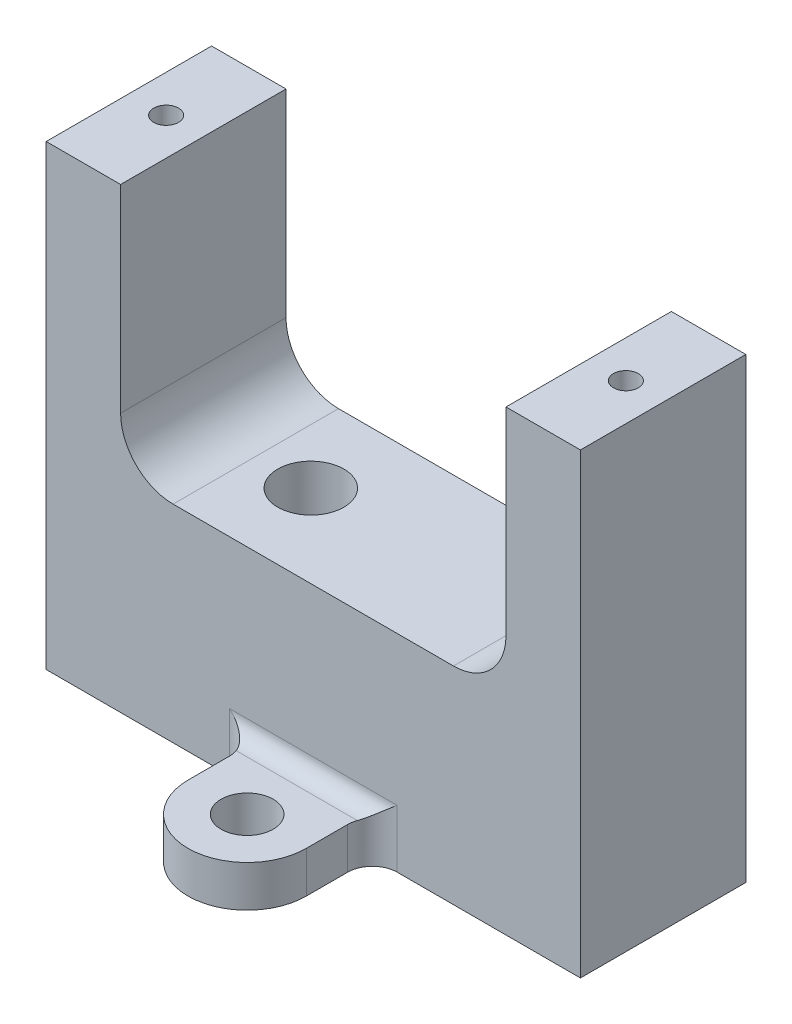
SolidWorks part; units mm, degrees
ref_plane "Front Plane" through (0, 0, 0) normal (0, 0, 1) x (1, 0, 0)
ref_plane "Top Plane" through (0, 0, 0) normal (0, 1, 0) x (1, 0, 0)
ref_plane "Right Plane" through (0, 0, 0) normal (1, 0, 0) x (0, 0, -1)
sketch "Sketch1" plane through (0, 0, 0) normal (0, 1, 0) x (1, 0, 0)
  line L0 (-16.15, 5) -> (-11.65, -5) construction
  line L1 (-16.15, 5) -> (-11.65, 5)
  line L2 (-16.15, 5) -> (-16.15, -5)
  line L3 (-16.15, -5) -> (-11.65, -5)
  line L4 (-11.65, 5) -> (-11.65, -5)
  line L5 (0, 0) -> (0, -5) construction
  line L6 (0, -5) -> (-11.65, -5) construction
  line L7 (16.15, 5) -> (11.65, -5) construction
  line L8 (11.65, 5) -> (11.65, -5)
  line L9 (16.15, -5) -> (11.65, -5)
  line L10 (16.15, 5) -> (16.15, -5)
  line L11 (16.15, 5) -> (11.65, 5)
  circle A0 centre (-13.9, 0) radius 0.75 construction
  circle A2 centre (13.9, 0) radius 0.75 construction
  dimension "D1" = 1.5
  dimension "D2" = 13.9
  dimension "D3" = 10
  dimension "D4" = 4.5
extrude "Boss-Extrude1" add sketch "Sketch1" against normal blind 15.15
hole_wizard "Ø1.5 (1.5) Diameter Hole1" positions "Sketch3" profile "Sketch4" hole size "Ø1.5" standard "ANSI Metric"
sketch "Sketch3" plane through (0, 0, 0) normal (0, 1, 0) x (1, 0, 0)
  line L0 (16.15, 5) -> (11.65, -5) construction
  point P0 (-13.9, 0)
  point P3 (13.9, 0)
sketch "Sketch4" plane through (-13.9, 0, 0) normal (1, 0, 0) x (0, 0, 1)
  line L0 (0, 0) -> (0, 8)
  line L1 (0, 8) -> (0.75, 7.5494)
  line L2 (0.75, 7.5494) -> (0.75, 0)
  line L5 (0.75, 0) -> (0, 0)
  line L10 (0, 8) -> (-0.75, 7.5494) construction
  line L11 (0, -6.35) -> (0, 107.95) construction
  dimension "Hole Dia." = 1.5
  dimension "Hole Depth" = 8
  dimension "Drill Angle" = 118
sketch "Sketch5" plane through (0, -15.15, 0) normal (0, -1, 0) x (1, 0, 0)
  line L4 (-16.15, 5) -> (-16.15, -5)
  line L5 (-16.15, -5) -> (-11.65, -5)
  line L6 (-11.65, -5) -> (-11.65, 5)
  line L7 (-11.65, 5) -> (-16.15, 5)
  line L8 (-16.15, 5) -> (-16.15, -5)
  line L9 (-16.15, -5) -> (16.15, -5)
  line L11 (16.15, 5) -> (-16.15, 5)
  line L12 (11.65, -5) -> (16.15, -5)
  line L13 (16.15, -5) -> (16.15, 5)
  line L14 (16.15, 5) -> (11.65, 5)
  line L15 (11.65, 5) -> (11.65, -5)
  line L17 (16.15, -5) -> (16.15, 5)
  circle A0 centre (-5.15, 0) radius 2
  circle A1 centre (-13.9, 0) radius 0.75 construction
  dimension "D1" = 4
  dimension "D2" = 8.75
  dimension "D3" = 0
  dimension "D4" = 0
extrude "Boss-Extrude2" add sketch "Sketch5" along normal blind 12.5
fillet "Fillet1" radius 3.175 2 edges at (11.65, -15.15, 0) (-11.65, -15.15, 0)
sketch "Sketch6" plane through (-16.15, 0, 0) normal (-1, 0, 0) x (0, 0, 1)
  line L0 (5, -15.15) -> (-5, -15.15) construction
  line L1 (5, -15.15) -> (-5, -15.15) construction
  circle A0 centre (-1.2, -20.65) radius 2
  dimension "D1" = 4
  dimension "D2" = 5.5
  dimension "D3" = 1.2
extrude "Cut-Extrude1" cut sketch "Sketch6" against normal blind 15.4
sketch "Sketch7" plane through (0, -27.65, 0) normal (0, -1, 0) x (1, 0, 0)
  line L0 (-16.15, -5) -> (16.15, -5) construction
  line L1 (16.15, 5) -> (-16.15, 5) construction
  line L2 (-3.575, -5) -> (3.575, -5)
  line L3 (3.575, 5) -> (-3.575, 5)
  line L4 (0, 0) -> (16.15, 0) construction
  line L5 (16.15, -5) -> (16.15, 5) construction
  line L6 (-3.575, 9) -> (-3.575, 5)
  line L7 (3.575, 9) -> (3.575, 5)
  line L8 (3.575, -5) -> (-3.575, -5)
  line L9 (3.575, -9) -> (3.575, -5)
  line L10 (-3.575, -9) -> (-3.575, -5)
  circle A0 centre (0, 9) radius 1.575
  arc A1 (3.575, 9) -> (-3.575, 9) centre (0, 9) ccw
  circle A2 centre (0, 9) radius 3.575 construction
  circle A3 centre (0, -9) radius 1.575
  arc A4 (3.575, -9) -> (-3.575, -9) centre (0, -9) cw
  line M6 (-16.15, -5) -> (16.15, -5)
  dimension "D1" = 3.15
  dimension "D2" = 2
  dimension "D3" = 4
extrude "Boss-Extrude3" add sketch "Sketch7" against normal blind 2.5 contours L7 A1 L6 L3 A0 | A4 L9 L10 A3 M6 region at (0, -27.65, -5.1042) region at (0, -27.65, 5.1042)
fillet "Fillet3" radius 1.5 4 edges at (3.575, -26.4, -5) (-3.575, -26.4, -5) (-3.575, -26.4, 5) (3.575, -26.4, 5)
fillet "Fillet4" radius 1 2 edges at (0, -25.15, 5) (0, -25.15, -5)
